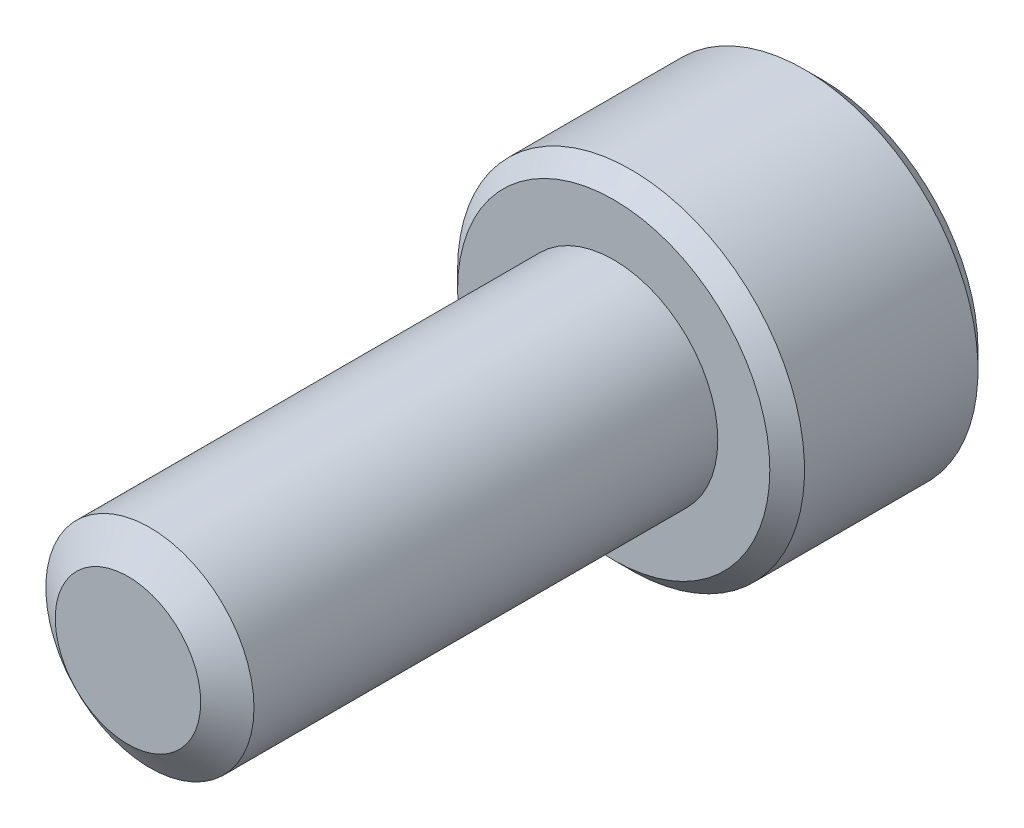
SolidWorks part; units mm, degrees
other "DetailItem1"
material "AISI 304"
ref_plane "Front Plane" through (0, 0, 0) normal (0, 0, 1) x (1, 0, 0)
ref_plane "Top Plane" through (0, 0, 0) normal (0, 1, 0) x (1, 0, 0)
ref_plane "Right Plane" through (0, 0, 0) normal (1, 0, 0) x (0, 0, -1)
sketch "Sketch1" plane through (0, 0, 0) normal (0, 0, 1) x (1, 0, 0)
  circle A0 centre (0, 0) radius 3
  dimension "OD" = 6
extrude "Extrude1" add sketch "Sketch1" against normal blind 14
sketch "Sketch2" plane through (0, 0, 0) normal (0, 0, 1) x (1, 0, 0)
  circle A0 centre (0, 0) radius 3 construction
  circle A1 centre (0, 0) radius 3
curve "Helix/Spiral1" [suppressed] pitch 1 height 15 turns 15 parameters "pitch"=1
sketch "Sketch3" plane through (0, 0, 0) normal (1, 0, 0) x (0, 0, -1)
  line L0 (-0.875, 3) -> (-0.5, 2.3505)
  line L1 (-0.5, 2.3505) -> (-0.375, 2.3505)
  line L2 (-0.375, 2.3505) -> (0, 3)
  line L3 (-0.875, 3) -> (0, 3)
  line L4 (-0.4375, 3) -> (-0.4375, 2.3505) construction
  line L5 (-0.6875, 2.6752) -> (-0.1875, 2.6752) construction
  line L6 (0, 3) -> (0, -3) construction
  dimension "D1" = 0.125
  dimension "D2" = 0.5
  dimension "D3" = 60
sweep "Cut-Sweep1" [suppressed] cut profiles "Sketch3" path "Helix/Spiral1"
sketch "Sketch4" plane through (0, 0, 0) normal (1, 0, 0) x (0, 0, -1)
  line L0 (0.6327, 3) -> (0, 2.0965)
  line L1 (0, 2.0965) -> (0, 3)
  line L2 (0.6327, 3) -> (0, 3)
  line L3 (-0.875, 3) -> (0, 3) construction
  line L4 (0, 0) -> (7.0209, 0) construction
  dimension "D1" = 55
  dimension "D2" = 0.254
revolve "Cut-Revolve1" cut sketch "Sketch4" angle 360 about L4
sketch "Sketch6" plane through (0, 0, -14) normal (0, 0, -1) x (-1, 0, 0)
  circle A0 centre (0, 0) radius 5
  dimension "head dia" = 10
extrude "Extrude2" add sketch "Sketch6" along normal blind 6
sketch "Sketch7" plane through (0, 0, -20) normal (0, 0, -1) x (-1, 0, 0)
  line L1 (0, 2.8868) -> (-2.5, 1.4434)
  line L2 (-2.5, 1.4434) -> (-2.5, -1.4434)
  line L3 (-2.5, -1.4434) -> (0, -2.8868)
  line L4 (0, -2.8868) -> (2.5, -1.4434)
  line L5 (2.5, -1.4434) -> (2.5, 1.4434)
  line L6 (2.5, 1.4434) -> (0, 2.8868)
  circle A0 centre (0, 0) radius 2.5 construction
  dimension "hex dia" = 5
extrude "Cut-Extrude1" cut sketch "Sketch7" against normal blind 3.75
sketch "Sketch8" plane through (0, 0, -20) normal (0, 0, -1) x (-1, 0, 0)
  circle A0 centre (0, 0) radius 2.8868
extrude "Cut-Extrude2" cut sketch "Sketch8" against normal through all draft 45
chamfer "Chamfer1" distance 0.5 angle 45 2 edges at (-5, 0, -20) (-5, 0, -14)
sketch "Sketch10" plane through (0, 0, -14) normal (0, 0, 1) x (1, 0, 0)
  circle A1 centre (0, 0) radius 3
  circle A2 centre (0, 0) radius 3
  dimension "D1" = 0
ref_plane "Plane1" through (0, 0, 0) normal (0, 0, 1) x (1, 0, 0)
extrude "partial thread" [suppressed] add sketch "Sketch10" along normal up to surface (31 mm away) separate body up to plane "Plane1"
chamfer "Chamfer2" [suppressed] distance 0.12 angle 45
combine bodies "Combine1" [suppressed] operation type add bodies to combine 107 108
sketch "Sketch9" plane through (0, 0, 0) normal (1, 0, 0) x (0, 0, -1)
  line L0 (0, 3) -> (0, -3) construction
  line L1 (2.5, 3) -> (2.5, -3) construction
  dimension "D1" = 2.5
equation "\"D3@Helix/Spiral1\" = \"screw length@Extrude1\"+\"pitch@Helix/Spiral1\""
equation "\"D1@Sketch3\" = \"pitch@Helix/Spiral1\"*.125"
equation "\"D2@Sketch3\" = \"pitch@Helix/Spiral1\"*.5"
equation "\"D1@Cut-Extrude1\" = \"hex dia@Sketch7\"*.75"
equation "\"D1@Chamfer1\" = \"head dia@Sketch6\"*.05"
equation "\"D1@Sketch9\" = \"pitch@Helix/Spiral1\"*2.5"
equation "\"D1@Chamfer2\"=\"OD@Sketch1\"*.02"
